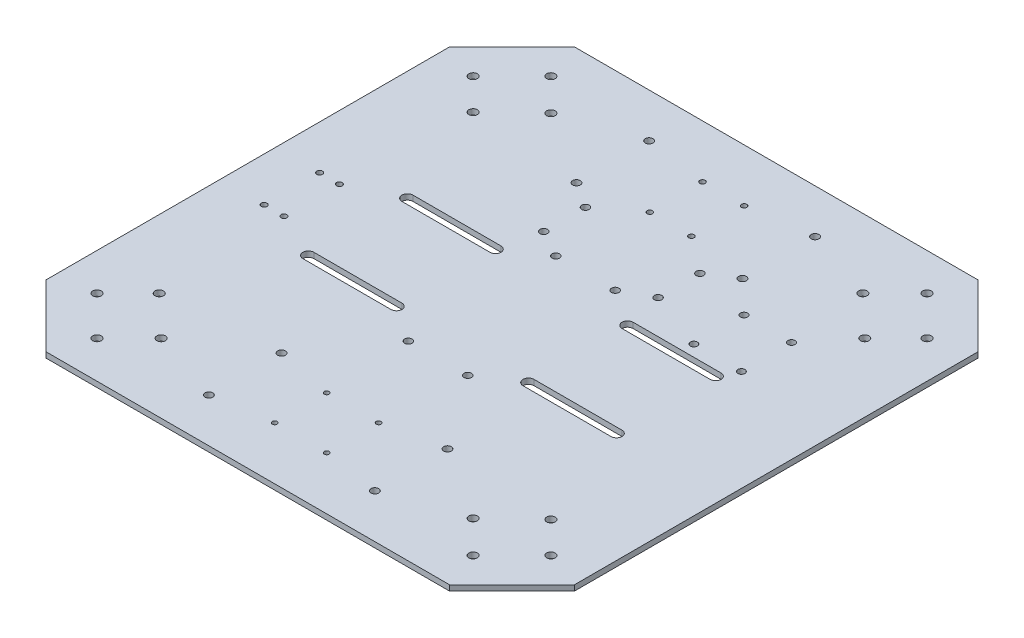
SolidWorks part; units mm, degrees
ref_plane "Front Plane" through (0, 0, 0) normal (0, 0, 1) x (1, 0, 0)
ref_plane "Top Plane" through (0, 0, 0) normal (0, 1, 0) x (1, 0, 0)
ref_plane "Right Plane" through (0, 0, 0) normal (1, 0, 0) x (0, 0, -1)
sketch "Sketch1" plane through (0, 0, 0) normal (0, 1, 0) x (1, 0, 0)
  line L0 (-61.766, 15.7353) -> (-25.845, 51.6564)
  line L1 (-61.766, 51.6564) -> (243.034, 51.6564)
  line L2 (-61.766, 51.6564) -> (-61.766, -253.1436)
  line L3 (-61.766, -253.1436) -> (243.034, -253.1436)
  line L4 (243.034, 51.6564) -> (243.034, -253.1436)
  line L5 (90.634, 95.069) -> (90.634, -294.9418) construction
  line L6 (-86.5248, -100.7436) -> (277.558, -100.7436) construction
  line L7 (243.034, 15.7353) -> (207.1129, 51.6564)
  line L8 (243.034, -217.2226) -> (207.1129, -253.1436)
  line L9 (-61.766, -217.2226) -> (-25.845, -253.1436)
  line L10 (128.734, -72.1686) -> (179.534, -72.1686) construction
  line L11 (128.734, -68.9936) -> (179.534, -68.9936)
  line L12 (128.734, -75.3436) -> (179.534, -75.3436)
  line L13 (128.734, -129.3186) -> (179.534, -129.3186) construction
  line L14 (128.734, -132.4936) -> (179.534, -132.4936)
  line L15 (128.734, -126.1436) -> (179.534, -126.1436)
  line L16 (52.534, -129.3186) -> (1.734, -129.3186) construction
  line L17 (52.534, -132.4936) -> (1.734, -132.4936)
  line L18 (52.534, -126.1436) -> (1.734, -126.1436)
  line L19 (52.534, -72.1686) -> (1.734, -72.1686) construction
  line L20 (52.534, -68.9936) -> (1.734, -68.9936)
  line L21 (52.534, -75.3436) -> (1.734, -75.3436)
  arc A0 (128.734, -68.9936) -> (128.734, -75.3436) centre (128.734, -72.1686) ccw
  arc A1 (179.534, -75.3436) -> (179.534, -68.9936) centre (179.534, -72.1686) ccw
  arc A2 (128.734, -132.4936) -> (128.734, -126.1436) centre (128.734, -129.3186) cw
  arc A3 (179.534, -126.1436) -> (179.534, -132.4936) centre (179.534, -129.3186) cw
  arc A4 (52.534, -132.4936) -> (52.534, -126.1436) centre (52.534, -129.3186) ccw
  arc A5 (1.734, -126.1436) -> (1.734, -132.4936) centre (1.734, -129.3186) ccw
  arc A6 (52.534, -68.9936) -> (52.534, -75.3436) centre (52.534, -72.1686) cw
  arc A7 (1.734, -75.3436) -> (1.734, -68.9936) centre (1.734, -72.1686) cw
  point P8 (90.634, 51.6564)
  point P11 (-61.766, -100.7436)
  point P18 (154.134, -72.1686)
  point P27 (154.134, -129.3186)
  point P34 (27.134, -129.3186)
  point P41 (27.134, -72.1686)
  dimension "D6" = 6.35
  dimension "D1" = 304.8
  dimension "D2" = 304.8
  dimension "D3" = 45
  dimension "D4" = 50.8
  dimension "D5" = 50.8
  dimension "D7" = 38.1
  dimension "D8" = 50.8
extrude "Boss-Extrude1" add sketch "Sketch1" along normal blind 3.175 contours L2 L9 L3 L8 L4 L7 L1 L0 A5 L18 A4 L17 A1 L12 A0 L11 L15 A3 L14 A2 L21 A7 L20 A6 region at (90.634, 0, 100.7436)
sketch "Sketch2" plane through (0, 3.175, 0) normal (0, 1, 0) x (1, 0, 0)
  line L0 (-40.323, 7.7627) -> (-22.3625, -10.1978) construction
  line L1 (-17.8724, 30.2133) -> (0.6409, 11.7001) construction
  line L2 (-43.8055, 33.6958) -> (20.8232, -30.9329) construction
  line L3 (-61.766, 15.7353) -> (-25.845, 51.6564) construction
  line L7 (90.634, 51.6564) -> (90.634, -253.1436) construction
  line L8 (-25.845, 51.6564) -> (207.1129, 51.6564) construction
  line L9 (-25.845, -253.1436) -> (207.1129, -253.1436) construction
  line L10 (-61.766, -100.7436) -> (243.034, -100.7436) construction
  line L11 (-61.766, 15.7353) -> (-61.766, -217.2226) construction
  line L12 (243.034, 15.7353) -> (243.034, -217.2226) construction
  circle A0 centre (-17.8724, 30.2133) radius 2.4638
  circle A1 centre (0.6409, 11.7001) radius 2.4638
  circle A2 centre (-22.3625, -10.1978) radius 2.4638
  circle A3 centre (-40.323, 7.7627) radius 2.4638
  circle A4 centre (203.6304, -10.1978) radius 2.4638
  circle A5 centre (221.5909, 7.7627) radius 2.4638
  circle A6 centre (180.627, 11.7001) radius 2.4638
  circle A7 centre (199.1403, 30.2133) radius 2.4638
  circle A8 centre (-22.3625, -191.2895) radius 2.4638
  circle A9 centre (-40.323, -209.25) radius 2.4638
  circle A10 centre (-17.8724, -231.7006) radius 2.4638
  circle A11 centre (0.6409, -213.1873) radius 2.4638
  circle A12 centre (221.5909, -209.25) radius 2.4638
  circle A13 centre (199.1403, -231.7006) radius 2.4638
  circle A14 centre (180.627, -213.1873) radius 2.4638
  circle A15 centre (203.6304, -191.2895) radius 2.4638
  dimension "D3" = 4.9276
  dimension "D4" = 4.9276
  dimension "D5" = 4.9276
  dimension "D6" = 4.9276
  dimension "D1" = 25.4
  dimension "D2" = 31.75
  dimension "D7" = 15.875
extrude "Cut-Extrude1" cut sketch "Sketch2" against normal blind 6.35
sketch "Sketch3" plane through (0, 3.175, 0) normal (0, 1, 0) x (1, 0, 0)
  line L0 (-61.766, -100.7436) -> (278.5513, -100.7436) construction
  line L2 (-61.766, 15.7353) -> (-61.766, -217.2226) construction
  line L3 (90.634, 51.6564) -> (90.634, -273.1997) construction
  line L4 (-25.845, 51.6564) -> (207.1129, 51.6564) construction
  circle A0 centre (73.362, -58.1986) radius 2.159
  circle A1 centre (107.652, -58.1986) radius 2.159
  circle A2 centre (73.362, -143.2886) radius 2.159
  circle A3 centre (107.652, -143.2886) radius 2.159
  point P10 (-61.766, -100.7436)
  dimension "D3" = 4.318
  dimension "D4" = 4.318
  dimension "D5" = 4.318
  dimension "D6" = 4.318
  dimension "D1" = 34.29
  dimension "D2" = 85.09
  dimension "D7" = 42.545
  dimension "D8" = 17.272
extrude "Cut-Extrude2" cut sketch "Sketch3" against normal blind 6.35
sketch "Sketch4" plane through (0, 3.175, 0) normal (0, 1, 0) x (1, 0, 0)
  line L0 (90.634, 51.6564) -> (90.634, -36.4614) construction
  line L1 (-25.845, 51.6564) -> (207.1129, 51.6564) construction
  line L2 (-61.766, -100.7436) -> (257.447, -100.7436) construction
  line L3 (-61.766, 15.7353) -> (-61.766, -217.2226) construction
  circle A0 centre (42.755, 26.2564) radius 2.2225
  circle A1 centre (138.513, 26.2564) radius 2.2225
  circle A2 centre (42.755, -15.6536) radius 2.2225
  circle A3 centre (138.513, -15.6536) radius 2.2225
  circle A4 centre (138.513, -185.8336) radius 2.2225
  circle A5 centre (42.755, -185.8336) radius 2.2225
  circle A6 centre (138.513, -227.7436) radius 2.2225
  circle A7 centre (42.755, -227.7436) radius 2.2225
  dimension "D1" = 4.445
  dimension "D2" = 4.445
  dimension "D3" = 4.445
  dimension "D4" = 4.445
  dimension "D5" = 95.758
  dimension "D6" = 41.91
  dimension "D7" = 47.879
  dimension "D8" = 25.4
extrude "Cut-Extrude3" cut sketch "Sketch4" against normal through all
sketch "Sketch5" plane through (0, 3.175, 0) normal (0, 1, 0) x (1, 0, 0)
  line L0 (-61.766, -100.7436) -> (105.2484, -100.7436) construction
  line L1 (-61.766, 15.7353) -> (-61.766, -217.2226) construction
  circle A0 centre (-36.366, -84.7416) radius 1.651
  circle A1 centre (-24.936, -84.7416) radius 1.651
  circle A2 centre (-24.936, -116.7456) radius 1.651
  circle A3 centre (-36.366, -116.7456) radius 1.651
  dimension "D1" = 3.302
  dimension "D2" = 3.302
  dimension "D3" = 11.43
  dimension "D4" = 16.002
  dimension "D5" = 25.4
extrude "Cut-Extrude4" cut sketch "Sketch5" against normal through all
sketch "Sketch6" plane through (0, 3.175, 0) normal (0, 1, 0) x (1, 0, 0)
  line L0 (243.034, 15.7353) -> (243.034, -217.2226) construction
  line L1 (-25.845, 51.6564) -> (207.1129, 51.6564) construction
  line L2 (90.634, 51.6564) -> (90.634, -253.1436) construction
  line L3 (-25.845, -253.1436) -> (207.1129, -253.1436) construction
  circle A0 centre (157.182, -33.4336) radius 2.032
  circle A1 centre (157.182, -62.3896) radius 2.032
  circle A2 centre (184.614, -62.3896) radius 2.032
  circle A3 centre (184.614, -33.4336) radius 2.032
  circle A4 centre (57.614, -25.3353) radius 2.159
  circle A5 centre (57.614, -49.4653) radius 2.159
  circle A6 centre (123.654, -49.4653) radius 2.159
  circle A7 centre (123.654, -25.3353) radius 2.159
  circle A8 centre (75.648, -192.6916) radius 1.397
  circle A9 centre (75.648, -222.6636) radius 1.397
  circle A10 centre (105.62, -222.6636) radius 1.397
  circle A11 centre (105.62, -192.6916) radius 1.397
  circle A12 centre (78.6339, 21.1764) radius 1.55
  circle A13 centre (78.6339, -9.2236) radius 1.55
  circle A14 centre (102.634, -9.2236) radius 1.55
  circle A15 centre (102.634, 21.1764) radius 1.55
  dimension "D1" = 4.064
  dimension "D6" = 4.318
  dimension "D7" = 4.318
  dimension "D10" = 2.794
  dimension "D11" = 2.794
  dimension "D15" = 3.1
  dimension "D16" = 3.1
  dimension "D2" = 27.432
  dimension "D3" = 28.956
  dimension "D4" = 58.42
  dimension "D5" = 85.09
  dimension "D8" = 33.02
  dimension "D9" = 24.13
  dimension "D12" = 14.986
  dimension "D13" = 29.972
  dimension "D14" = 30.48
  dimension "D17" = 30.4
  dimension "D18" = 24
  dimension "D19" = 30.48
extrude "Cut-Extrude5" cut sketch "Sketch6" against normal through all
